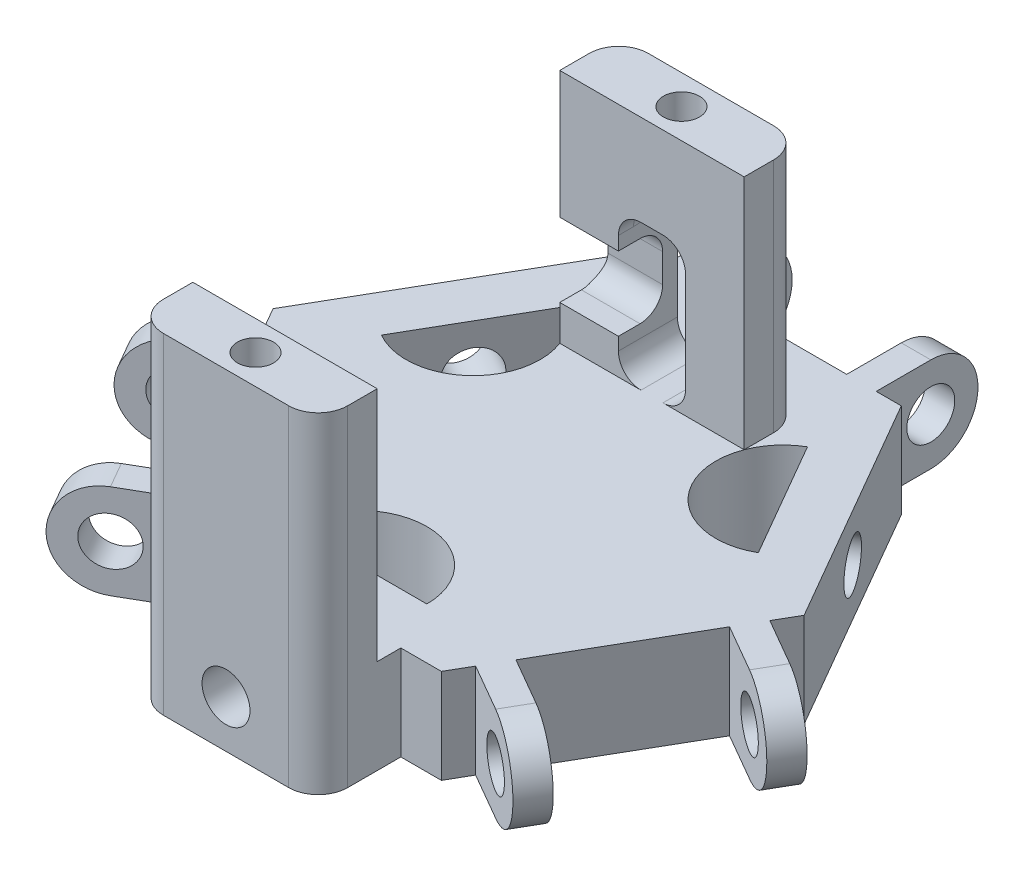
SolidWorks part; units mm, degrees
ref_plane "Piano frontale" through (0, 0, 0) normal (0, 0, 1) x (1, 0, 0)
ref_plane "Piano superiore" through (0, 0, 0) normal (0, 1, 0) x (1, 0, 0)
ref_plane "Piano destro" through (0, 0, 0) normal (1, 0, 0) x (0, 0, -1)
sketch "Schizzo1" plane through (0, 0, 0) normal (0, 1, 0) x (1, 0, 0)
  line L0 (-25.9007, 0) -> (24.7765, 0) construction
  line L1 (18, 0) -> (9, 15.5885)
  line L2 (9, 15.5885) -> (-9, 15.5885)
  line L3 (-9, 15.5885) -> (-18, 0)
  line L4 (-18, 0) -> (-9, -15.5885)
  line L5 (-9, -15.5885) -> (9, -15.5885)
  line L6 (9, -15.5885) -> (18, 0)
  circle A0 centre (0, 0) radius 15.5885 construction
  dimension "D1" = 18
extrude "Estrusione-Estrusione1" add sketch "Schizzo1" along normal blind 6.4
sketch "Schizzo2" plane through (0, 6.4, 0) normal (0, 1, 0) x (1, 0, 0)
  line L0 (-4.55, -12.125) -> (4.55, -12.125)
  line L1 (-7.6422, 0) -> (9.3711, 0) construction
  line L2 (0, 2.5203) -> (0, -4.0345) construction
  arc A0 (-4.55, -12.125) -> (4.55, -12.125) centre (0, -12.125) cw
  dimension "D2" = 4.55
  dimension "D1" = 12.125
ref_axis "Assi1" through (0, -0.32, 0) along (0, 1, 0)
extrude "Taglio-Estrusione1" cut sketch "Schizzo2" against normal up to next
sketch "Schizzo3" plane through (-13.5, 0, 7.7942) normal (-0.866, 0, 0.5) x (0.5, 0, 0.866)
  line L0 (-9, 0) -> (9, 0) construction
  line L1 (-7.3, 6.4) -> (-5.3, 6.4)
  line L2 (-7.3, 6.4) -> (-7.3, 0)
  line L3 (-7.3, 0) -> (-5.3, 0)
  line L4 (-5.3, 6.4) -> (-5.3, 0)
  line L6 (7.3, 6.4) -> (5.3, 6.4)
  line L7 (7.3, 6.4) -> (7.3, 0)
  line L8 (7.3, 0) -> (5.3, 0)
  line L9 (5.3, 6.4) -> (5.3, 0)
  line L10 (-9, 6.4) -> (9, 6.4) construction
  line L11 (0, 0) -> (0, 6.4) construction
  dimension "D1" = 2
  dimension "D2" = 10.6
extrude "Estrusione-Estrusione2" add sketch "Schizzo3" along normal blind 6.9
sketch "Schizzo4" plane through (3.65, 0, 6.322) normal (0.5, 0, 0.866) x (0.866, 0, -0.5)
  line L3 (-15.5885, 0) -> (-15.5885, 6.4) construction
  line L10 (-22.4885, 6.4) -> (-15.5885, 6.4) construction
  line L11 (-22.4885, 0) -> (-15.5885, 0) construction
  line L12 (-19.2885, 6.4) -> (-19.2885, 0) construction
  circle A0 centre (-19.2885, 3.2) radius 1.625
  dimension "D1" = 3.25
  dimension "D2" = 3.7
extrude "Taglio-Estrusione2" cut sketch "Schizzo4" against normal up to surface (14.6 mm away) up to face at (-20.1378, 3.2, 3.1972)
fillet "Raccordo2" 2 edges at (-22.6256, 6.4, 5.7883) (-22.6256, 0, 5.7883) type full round first side face at (0, 6.4, 9.85) second side face at (0, 0, 9.85) middle face at (-22.6256, 3.2, 5.7883)
fillet "Raccordo3" 2 edges at (-16.3256, 6.4, 16.7002) (-16.3256, 0, 16.7002) type full round first side face at (0, 6.4, 9.85) second side face at (0, 0, 9.85) middle face at (-16.3256, 3.2, 16.7002)
sketch "Schizzo5" plane through (0, 0, 15.5885) normal (0, 0, 1) x (1, 0, 0)
  line L0 (0, 0) -> (0, 6.4) construction
  line L1 (-9, 0) -> (9, 0) construction
  line L2 (-9, 6.4) -> (9, 6.4) construction
  circle A0 centre (0, 3.2) radius 1.625
  dimension "D1" = 3.25
extrude "Taglio-Estrusione3" cut sketch "Schizzo5" against normal up to next
pattern_circular "RipetizioneCircolare1" count 3 over 360 about axis through (0, -0.32, 0) along (0, 1, 0) of "Estrusione-Estrusione2", "Taglio-Estrusione1", "Taglio-Estrusione2", "Raccordo2", "Raccordo3", "Taglio-Estrusione3"
sketch "Schizzo6" plane through (0, 0, 15.5885) normal (0, 0, 1) x (1, 0, 0)
  line L0 (-9, 6.4) -> (9, 6.4) construction
  line L1 (-6.25, 6.4) -> (6.25, 6.4)
  line L2 (-6.25, 6.4) -> (-6.25, 0)
  line L3 (-6.25, 0) -> (6.25, 0)
  line L4 (6.25, 6.4) -> (6.25, 0)
  line L5 (-9, 0) -> (9, 0) construction
  line L6 (0, -0.4417) -> (0, 6.8417) construction
  circle A0 centre (0, 3.2) radius 1.625
  circle A1 centre (0, 3.2) radius 1.625 construction
  point P11 (0, 6.4)
  dimension "D1" = 12.5
extrude "Estrusione-Estrusione3" add sketch "Schizzo6" along normal blind 5.6
sketch "Schizzo7" plane through (0, 6.4, 0) normal (0, 1, 0) x (1, 0, 0)
  line L0 (-6.25, -21.1885) -> (-6.25, -15.5885) construction
  line L1 (-6.25, -17.1885) -> (6.25, -17.1885)
  line L2 (-6.25, -17.1885) -> (-6.25, -21.1885)
  line L3 (-6.25, -21.1885) -> (6.25, -21.1885)
  line L4 (6.25, -17.1885) -> (6.25, -21.1885)
  line L6 (6.25, 7.6858) -> (-6.25, 7.6858)
  line L7 (6.25, 7.6858) -> (6.25, 11.6858)
  line L8 (6.25, 11.6858) -> (-6.25, 11.6858)
  line L9 (-6.25, 7.6858) -> (-6.25, 11.6858)
  arc A0 (-12.7756, 2.1221) -> (-8.2256, 10.0029) centre (-10.5006, 6.0625) ccw construction
  dimension "D1" = 4
extrude "Estrusione-Estrusione4" add sketch "Schizzo7" along normal blind 16.02
fillet "Raccordo4" radius 2 4 edges at (6.25, 11.21, 21.1885) (-6.25, 11.21, 21.1885) (6.25, 14.41, -11.6858) (-6.25, 14.41, -11.6858)
sketch "Schizzo8" plane through (0, 22.42, 0) normal (0, 1, 0) x (1, 0, 0)
  line L0 (0, -33.7522) -> (0, 14.7049) construction
  line L3 (-6.25, -19.1885) -> (6.25, -19.1885) construction
  line L4 (-6.25, -17.1885) -> (-6.25, -19.1885) construction
  line L5 (6.25, -19.1885) -> (6.25, -17.1885) construction
  line L6 (6.25, 9.6858) -> (-6.25, 9.6858) construction
  circle A0 centre (0, -19.1885) radius 1.225
  circle A1 centre (0, 9.6858) radius 1.225
  arc A2 (4.25, -21.1885) -> (6.25, -19.1885) centre (4.25, -19.1885) ccw construction
  arc A3 (-4.25, 11.6858) -> (-6.25, 9.6858) centre (-4.25, 9.6858) ccw construction
  dimension "D1" = 2.45
extrude "Taglio-Estrusione4" cut sketch "Schizzo8" against normal blind 9
sketch "Schizzo9" plane through (0, 0, -11.6858) normal (0, 0, -1) x (-1, 0, 0)
  line L0 (-4.25, 6.4) -> (4.25, 6.4) construction
  line L1 (2.275, 16.25) -> (-2.275, 16.25)
  line L2 (2.275, 16.25) -> (2.275, 6.4)
  line L3 (2.275, 6.4) -> (-2.275, 6.4)
  line L4 (-2.275, 16.25) -> (-2.275, 6.4)
  line L5 (0, -0.32) -> (0, 6.72) construction
  point P9 (0, 16.25)
  dimension "D1" = 9.85
  dimension "D2" = 4.55
extrude "Taglio-Estrusione5" cut sketch "Schizzo9" against normal up to next
sketch "Schizzo11" plane through (-6.25, 0, 0) normal (-1, 0, 0) x (0, 0, 1)
  line L0 (-7.6858, 22.42) -> (-7.6858, 6.4) construction
  line L1 (-7.6858, 8.8) -> (-10.6847, 8.8)
  line L2 (-7.6858, 8.8) -> (-7.6858, 13.8)
  line L3 (-7.6858, 13.8) -> (-10.6847, 13.8)
  line L4 (-10.6847, 8.8) -> (-10.6847, 13.8)
  line L5 (-9.6858, 6.4) -> (-7.6858, 6.4) construction
  point P6 (-9.1853, 8.8)
  dimension "D1" = 5
  dimension "D2" = 2.4
extrude "Taglio-Estrusione6" cut sketch "Schizzo11" against normal up to surface (3.975 mm away) up to face at (-2.275, 11.325, -9.6858)
fillet "Raccordo5" radius 1.53 6 edges at (2.275, 16.25, -9.6858) (-4.1289, 13.8, -10.6847) (-4.1289, 8.8, -10.6847) (-2.275, 16.25, -9.6858) (2.275, 6.4, -9.6858) (-2.275, 6.4, -9.6858)
sketch "Schizzo12" plane through (6.25, 0, 0) normal (1, 0, 0) x (0, 0, -1)
  circle A0 centre (0, -120) radius 75 construction
  dimension "D1" = 150
  dimension "D2" = 120
ref_plane "Piano1" through (0, -180, 0) normal (0, -1, 0) x (-1, 0, 0)
sketch "Schizzo13" plane through (0, -180, 0) normal (0, -1, 0) x (-1, 0, 0)
  circle A0 centre (0, 0) radius 125 construction
  dimension "D1" = 250
